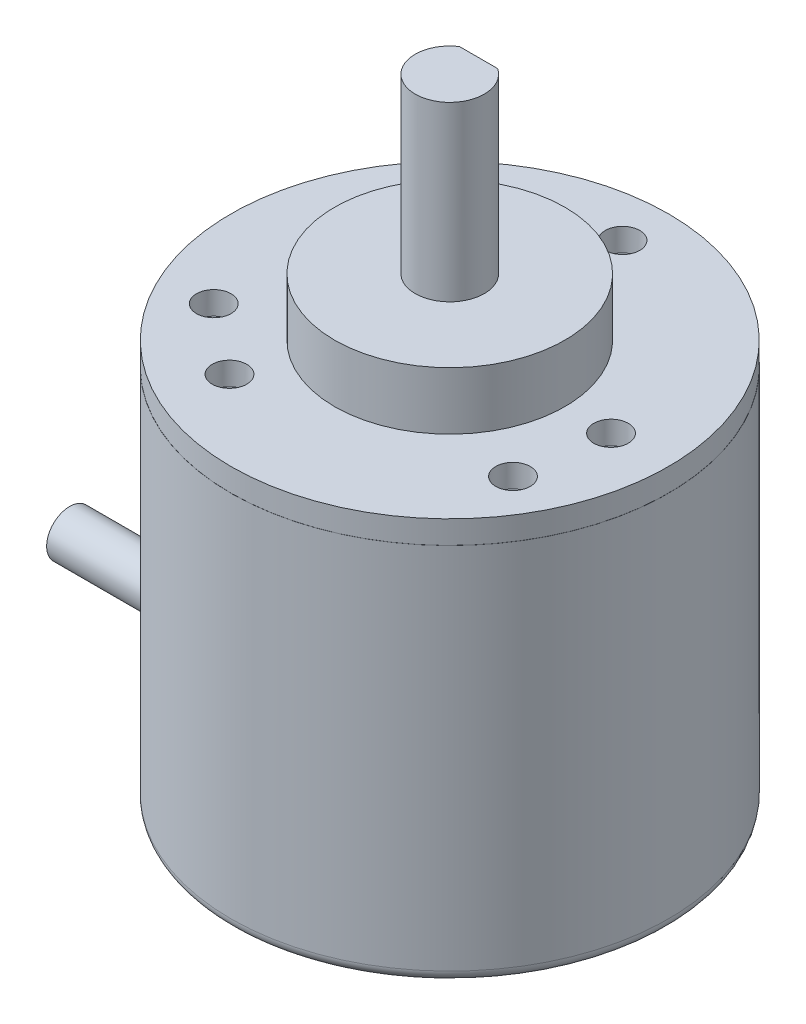
SolidWorks part; units mm, degrees
ref_plane "Plan de face" through (0, 0, 0) normal (0, 0, 1) x (1, 0, 0)
ref_plane "Plan de dessus" through (0, 0, 0) normal (0, 1, 0) x (1, 0, 0)
ref_plane "Plan de droite" through (0, 0, 0) normal (1, 0, 0) x (0, 0, -1)
sketch "Esquisse1" plane through (0, 0, 0) normal (0, 1, 0) x (1, 0, 0)
  circle A0 centre (0, 0) radius 19
  dimension "D1" = 38
extrude "Boss.-Extru.1" add sketch "Esquisse1" along normal blind 31
sketch "Esquisse2" plane through (0, 31, 0) normal (0, 1, 0) x (1, 0, 0)
  circle A0 centre (0, 0) radius 10
  dimension "D1" = 20
extrude "Boss.-Extru.2" add sketch "Esquisse2" along normal blind 5
sketch "Esquisse3" plane through (0, 36, 0) normal (0, 1, 0) x (1, 0, 0)
  circle A0 centre (0, 0) radius 3
  dimension "D1" = 6
extrude "Boss.-Extru.3" add sketch "Esquisse3" along normal blind 15
sketch "Esquisse4" plane through (0, 51, 0) normal (0, 1, 0) x (1, 0, 0)
  line L0 (1.6583, 2.5) -> (-1.6583, 2.5)
  line L1 (-3.4172, 3) -> (5.2185, 3) construction
  arc A0 (-1.6583, 2.5) -> (1.6583, 2.5) centre (0, 0) cw
  circle A1 centre (0, 0) radius 3 construction
  dimension "D1" = 0.5
extrude "Enlèv. mat.-Extru.1" cut sketch "Esquisse4" against normal blind 10
sketch "Esquisse5" plane through (0, 31, 0) normal (0, 1, 0) x (1, 0, 0)
  line L0 (-22.3839, 0) -> (23.6554, 0) construction
  line L1 (0, 0) -> (22.18, -12.8056) construction
  line L2 (0, 0) -> (-14, -24.2487) construction
  line L3 (0, 0) -> (-20.4122, -11.785) construction
  line L4 (0, 0) -> (0, 20.4766) construction
  line L5 (0, 0) -> (-11.2247, 19.4417) construction
  circle A0 centre (14, 0) radius 1.5
  circle A1 centre (12.9904, -7.5) radius 1.5
  circle A2 centre (0, 0) radius 14 construction
  circle A3 centre (0, 0) radius 15 construction
  circle A4 centre (-7, -12.1244) radius 1.5
  circle A5 centre (-12.9904, -7.5) radius 1.5
  circle A6 centre (0, 15) radius 1.5
  circle A7 centre (-7, 12.1244) radius 1.5
  dimension "D2" = 1
  dimension "D3" = 3
  dimension "D4" = 3
  dimension "D7" = 28
  dimension "D8" = 3
  dimension "D9" = 3
  dimension "D11" = 3
  dimension "D12" = 3
  dimension "D1" = 30
  dimension "D5" = 60
  dimension "D6" = 30
  dimension "D10" = 30
extrude "Enlèv. mat.-Extru.2" cut sketch "Esquisse5" against normal blind 5
sketch "Esquisse6" plane through (0, 0, 0) normal (1, 0, 0) x (0, 0, -1)
  line L0 (10, 31) -> (-10, 31) construction
  circle A0 centre (0, 0) radius 4
  dimension "D2" = 8
  dimension "D1" = 31
extrude "Boss.-Extru.4" add sketch "Esquisse6" against normal blind 20
sketch "Esquisse7" plane through (-20, 0, 0) normal (-1, 0, 0) x (0, 0, 1)
  circle A0 centre (0, 0) radius 2.5
  dimension "D1" = 5
extrude "Boss.-Extru.5" add sketch "Esquisse7" along normal blind 3
sketch "Esquisse8" plane through (-23, 0, 0) normal (-1, 0, 0) x (0, 0, 1)
  circle A0 centre (0, 0) radius 2
  dimension "D1" = 4
extrude "Boss.-Extru.6" add sketch "Esquisse8" along normal blind 10
sketch "Esquisse10" plane through (0, 0, 0) normal (0, -1, 0) x (1, 0, 0)
  circle A0 centre (0, 0) radius 19.01
  circle A1 centre (0, 0) radius 19 construction
  dimension "D1" = 0.01
extrude "Boss.-Extru.7" add sketch "Esquisse10" against normal blind 29 and the other way blind 4
fillet "Congé1" radius 1 1 edges at (0, -4, -19.01)
